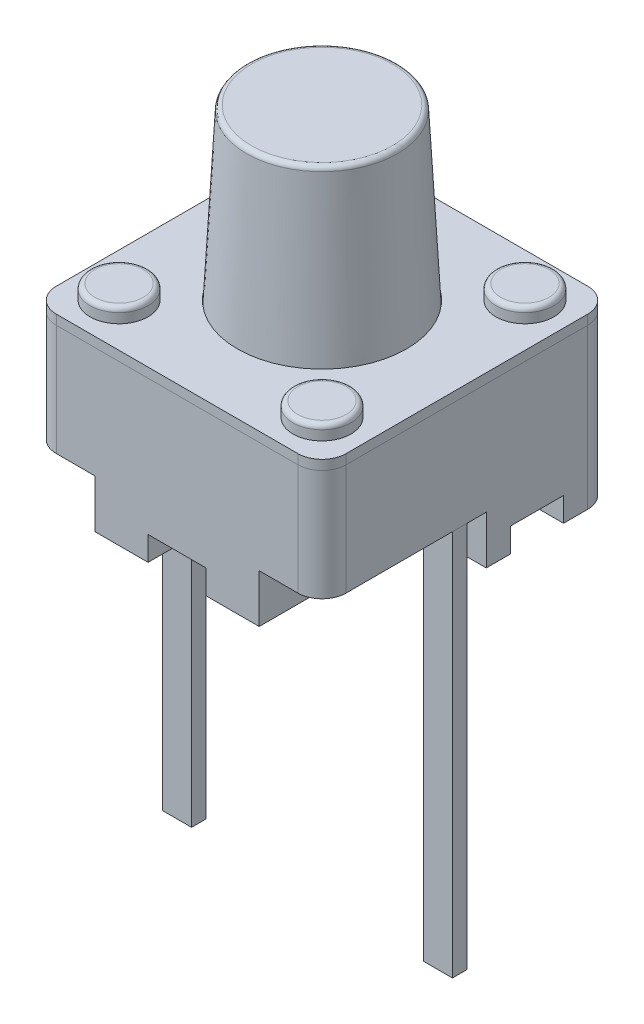
SolidWorks part; units mm, degrees
note: The reader was unsure of these and kept them because the rebuilt part matched: shared geometry of "Sketch1<3>", "Sketch1<4>", "Sketch1<5>", "Sketch2<3>", "Sketch1<7>".
material "Custom Plastic"
ref_plane "Front Plane" through (0, 0, 0) normal (0, 0, 1) x (1, 0, 0)
ref_plane "Top Plane" through (0, 0, 0) normal (0, 1, 0) x (1, 0, 0)
ref_plane "Right Plane" through (0, 0, 0) normal (1, 0, 0) x (0, 0, -1)
sketch "Sketch1" plane through (0, 0, 0) normal (0, 1, 0) x (1, 0, 0)
  line L0 (-3.2652, 0) -> (3.207, 0) construction
  line L1 (-2.5, 3) -> (2.5, 3)
  line L2 (-3, 2.5) -> (-3, -2.5)
  line L3 (-2.5, -3) -> (2.5, -3)
  line L4 (3, 2.5) -> (3, -2.5)
  line L5 (-3, 3) -> (3, -3) construction
  line L6 (-3, -3) -> (3, 3) construction
  line L7 (0, -3.1905) -> (0, 3.2124) construction
  line L8 (3, 0) -> (2.4, 0)
  line L9 (3, 0) -> (3, -0.3)
  line L10 (3, -0.3) -> (2.4, -0.3)
  line L11 (2.4, 0) -> (2.4, -0.3)
  line L12 (-3, -0.3) -> (-2.4, -0.3)
  line L13 (-2.4, 0) -> (-2.4, -0.3)
  line L14 (-3, 0) -> (-2.4, 0)
  circle A0 centre (2.1, 2.1) radius 0.6
  circle A1 centre (2.1, -2.1) radius 0.6
  circle A2 centre (-2.1, -2.1) radius 0.6
  circle A3 centre (-2.1, 2.1) radius 0.6
  circle A4 centre (0, 0) radius 1.75
  arc A5 (2.5, 3) -> (3, 2.5) centre (2.5, 2.5) cw
  arc A6 (2.5, -3) -> (3, -2.5) centre (2.5, -2.5) ccw
  arc A7 (-3, -2.5) -> (-2.5, -3) centre (-2.5, -2.5) ccw
  arc A8 (-2.5, 3) -> (-3, 2.5) centre (-2.5, 2.5) ccw
  point P0 (0, 0)
  point P1 (0, 0)
  point P9 (0, 0)
  point P18 (0, 0)
  dimension "D1" = 6
  dimension "D2" = 0.9
  dimension "D3" = 1.2
  dimension "D5" = 3.5
  dimension "D6" = 0.5
  dimension "D7" = 0.6
  dimension "D8" = 0.3
  dimension "D4" = 4
extrude "Base" add sketch "Sketch1" along normal blind 3.3 contours L14 L2 L12 L13 | L1 A8 L2 L14 L13 L12 A7 L3 A6 L4 L10 L11 L8 A5 A0 A1 A2 A3 A4 | A3 | A2 | A4 | A1 | L8 L11 L10 L4 | A0
extrude "Top Plate" add sketch "Sketch1<3>" along normal blind 0.2 from surface at 3.3 separate body contours L1 A8 L2 L14 L13 L12 A7 L3 A6 L4 L10 L11 L8 A5 A0 A1 A2 A3 A4 | L8 L11 L10 L4 | L14 L2 L12 L13 starting at face at (0, 3.3, 0)
sketch "Sketch1<3>" plane through (0, 0, 0) normal (0, 1, 0) x (1, 0, 0) same geometry as "Sketch1"
extrude "Knobs" add sketch "Sketch1<4>" along normal blind 0.5 from offset 3.3 contours A1 | A2 | A3 | A0
sketch "Sketch1<4>" plane through (0, 0, 0) normal (0, 1, 0) x (1, 0, 0) same geometry as "Sketch1"
extrude "Actuator" add sketch "Sketch1<5>" along normal blind 3.7 draft 3 from surface at 3.3 separate body contours A4 starting at face at (-2.1, 3.3, -1.5)
sketch "Sketch1<5>" plane through (0, 0, 0) normal (0, 1, 0) x (1, 0, 0) same geometry as "Sketch1"
sketch "Sketch2" plane through (0, 0, 0) normal (0, -1, 0) x (1, 0, 0)
  line L0 (0, 3) -> (0.6, 3)
  line L1 (0, 3) -> (0, -3) construction
  line L2 (-2.5, 3) -> (2.5, 3) construction
  line L3 (0.6, 3) -> (1.7, 3)
  line L4 (0, -3) -> (0.6, -3)
  line L5 (-1.7, -2) -> (-3, -2)
  line L6 (0.6, -3) -> (0.6, 3)
  line L7 (-1.7, -0.9) -> (-1.7, -2)
  line L8 (-1.7, -0.9) -> (-3, -0.9)
  line L9 (1.7, -0.9) -> (3, -0.9)
  line L10 (1.7, -0.9) -> (1.7, -2)
  line L11 (-3, -0.4) -> (-1.7, -0.4)
  line L12 (-0.6, -3) -> (-0.6, 3)
  line L13 (1.7, 3) -> (1.7, -0.4)
  line L14 (-1.7, 3) -> (-1.7, -0.4)
  line L15 (3, 0) -> (-3, 0) construction
  line L16 (-3, -2.5) -> (-3, 2.5) construction
  line L21 (-2.5, -3) -> (2.5, -3) construction
  line L22 (1.7, -2) -> (3, -2)
  line L23 (3, -2.5) -> (3, 2.5) construction
  line L25 (3, -0.4) -> (1.7, -0.4)
  point P5 (0, 0)
  point P12 (0, 0)
  arc M1 (3, 2.5) -> (2.5, 3) centre (2.5, 2.5) ccw
  line M2 (2.5, 3) -> (-2.5, 3)
  arc M3 (-2.5, 3) -> (-3, 2.5) centre (-2.5, 2.5) ccw
  line M4 (-3, 2.5) -> (-3, -2.5)
  line M6 (-2.5, -3) -> (2.5, -3)
  line M8 (3, -2.5) -> (3, 2.5)
  dimension "D1" = 0.6
  dimension "D2" = 1.7
  dimension "D3" = 0.4
  dimension "D4" = 1
  dimension "D6" = 0.5
extrude "Base Leg Cutout" cut sketch "Sketch2" against normal blind 1 from surface at 0 contours L14 L11 M2 M3 M4 | L25 L13 M8 M1 M2 starting at face at (0, 0, 0)
extrude "Base Shallow Cutout" cut sketch "Sketch2<3>" against normal blind 0.5 contours L1 L12 M2 M6 | L10 L22 L9 M8 | L7 L8 L5 M4
sketch "Sketch2<3>" plane through (0, 0, 0) normal (0, -1, 0) x (1, 0, 0) same geometry as "Sketch2"
extrude "Pins" add sketch "Sketch1<7>" against normal blind 8 from offset 1 separate body contours L14 L2 L12 L13 | L8 L11 L10 L4
sketch "Sketch1<7>" plane through (0, 0, 0) normal (0, 1, 0) x (1, 0, 0) same geometry as "Sketch1"
fillet "Fillet1" radius 0.1 1 edges at (0, 7, 1.5561)
fillet "Fillet2" radius 0.1 4 edges at (-2.1, 3.8, -1.5) (2.1, 3.8, -1.5) (-2.1, 3.8, 2.7) (2.1, 3.8, 2.7)
